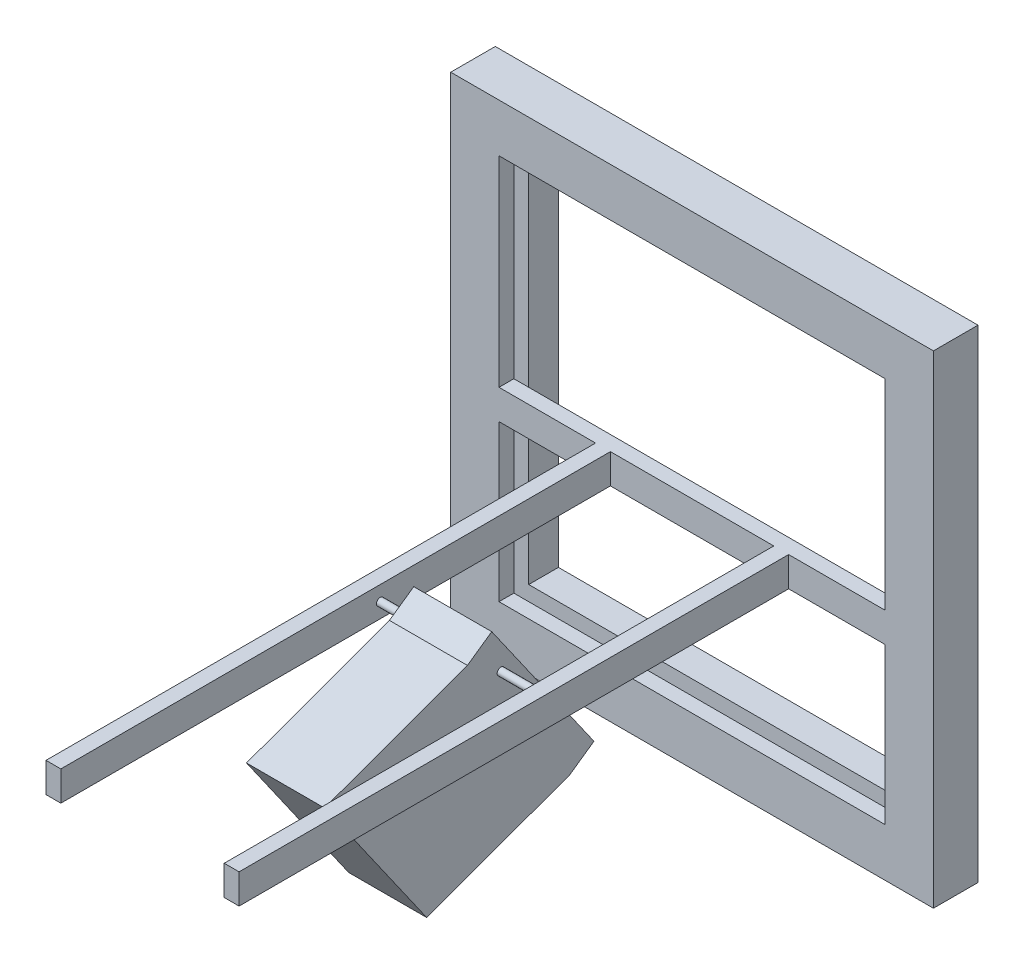
SolidWorks part; units mm, degrees
ref_plane "Front Plane" through (0, 0, 0) normal (0, 0, 1) x (1, 0, 0)
ref_plane "Top Plane" through (0, 0, 0) normal (0, 1, 0) x (1, 0, 0)
ref_plane "Right Plane" through (0, 0, 0) normal (1, 0, 0) x (0, 0, -1)
sketch "Sketch1" plane through (0, 0, 0) normal (0, 0, 1) x (1, 0, 0)
  line L0 (25.4, 25.4) -> (635, 25.4)
  line L1 (0, 0) -> (660.4, 0)
  line L2 (0, 0) -> (0, 660.4)
  line L3 (0, 660.4) -> (660.4, 660.4)
  line L4 (660.4, 0) -> (660.4, 660.4)
  line L5 (635, 25.4) -> (635, 635)
  line L6 (25.4, 635) -> (635, 635)
  line L7 (25.4, 25.4) -> (25.4, 635)
  dimension "D1" = 660.4
  dimension "D2" = 25.4
extrude "Boss-Extrude1" add sketch "Sketch1" along normal blind 50.8
sketch "Sketch2" plane through (0, 0, 50.8) normal (0, 0, 1) x (1, 0, 0)
  line L0 (0, 660.4) -> (0, 0) construction
  line L1 (0, 317.5) -> (660.4, 317.5)
  line L2 (0, 317.5) -> (0, 266.7)
  line L3 (0, 266.7) -> (660.4, 266.7)
  line L4 (660.4, 317.5) -> (660.4, 266.7)
  line L5 (660.4, 0) -> (660.4, 660.4) construction
  line L6 (0, 0) -> (660.4, 0) construction
  dimension "D1" = 266.7
  dimension "D2" = 50.8
extrude "Boss-Extrude2" add sketch "Sketch2" along normal blind 25.4
sketch "Sketch3" plane through (0, 0, 76.2) normal (0, 0, 1) x (1, 0, 0)
  line L0 (660.4, 317.5) -> (0, 317.5) construction
  line L1 (165.1, 317.5) -> (190.5, 317.5)
  line L2 (165.1, 317.5) -> (165.1, 266.7)
  line L3 (165.1, 266.7) -> (190.5, 266.7)
  line L4 (190.5, 317.5) -> (190.5, 266.7)
  line L5 (0, 266.7) -> (660.4, 266.7) construction
  line L6 (0, 317.5) -> (0, 266.7) construction
  line L7 (469.9, 317.5) -> (495.3, 317.5)
  line L8 (469.9, 317.5) -> (469.9, 266.7)
  line L9 (469.9, 266.7) -> (495.3, 266.7)
  line L10 (495.3, 317.5) -> (495.3, 266.7)
  dimension "D1" = 279.4
  dimension "D2" = 25.4
  dimension "D3" = 190.5
extrude "Boss-Extrude3" add sketch "Sketch3" along normal blind 939.8
sketch "Sketch4" plane through (469.9, 0, 0) normal (-1, 0, 0) x (0, 0, 1)
  line L0 (485.5156, 358.685) -> (310.6895, 109.0075)
  line L1 (310.6895, 109.0075) -> (352.3025, 79.8698)
  line L2 (352.3025, 79.8698) -> (596.7128, -9.0883)
  line L3 (596.7128, -9.0883) -> (771.5389, 240.5892)
  line L4 (771.5389, 240.5892) -> (527.1286, 329.5473)
  line L5 (527.1286, 329.5473) -> (485.5156, 358.685)
  line L8 (50.8, 660.4) -> (50.8, 317.5) construction
  line L9 (1016, 317.5) -> (76.2, 317.5) construction
  line L10 (50.8, 266.7) -> (50.8, 0) construction
  circle A0 centre (469.9, 292.1) radius 6.35
  dimension "D7" = 12.7
  dimension "D1" = 35
  dimension "D2" = 50.8
  dimension "D3" = 304.8
  dimension "D4" = 15
  dimension "D5" = 260.096
  dimension "D6" = 25.4
  dimension "D8" = 63.5
  dimension "D9" = 25.4
  dimension "D10" = 419.1
extrude "Boss-Extrude4" add sketch "Sketch4" along normal blind 133.35 from offset 73.025 separate body
extrude "Boss-Extrude5" add sketch "Sketch4<2>" along normal blind 282.956 contours A0 region at (469.9, 292.1, 469.9)
sketch "Sketch4<2>" plane through (469.9, 0, 0) normal (-1, 0, 0) x (0, 0, 1) same geometry as "Sketch4"
sketch "Sketch5" plane through (0, 0, 0) normal (0, 0, 1) x (1, 0, 0)
  line L0 (-82.55, 742.95) -> (742.95, 742.95)
  line L1 (0, 660.4) -> (660.4, 660.4)
  line L2 (0, 660.4) -> (0, 0)
  line L3 (0, 0) -> (660.4, 0)
  line L4 (660.4, 660.4) -> (660.4, 0)
  line L5 (742.95, 742.95) -> (742.95, -82.55)
  line L6 (-82.55, -82.55) -> (742.95, -82.55)
  line L7 (-82.55, 742.95) -> (-82.55, -82.55)
  dimension "D1" = 82.55
extrude "Boss-Extrude6" add sketch "Sketch5" along normal blind 76.2
